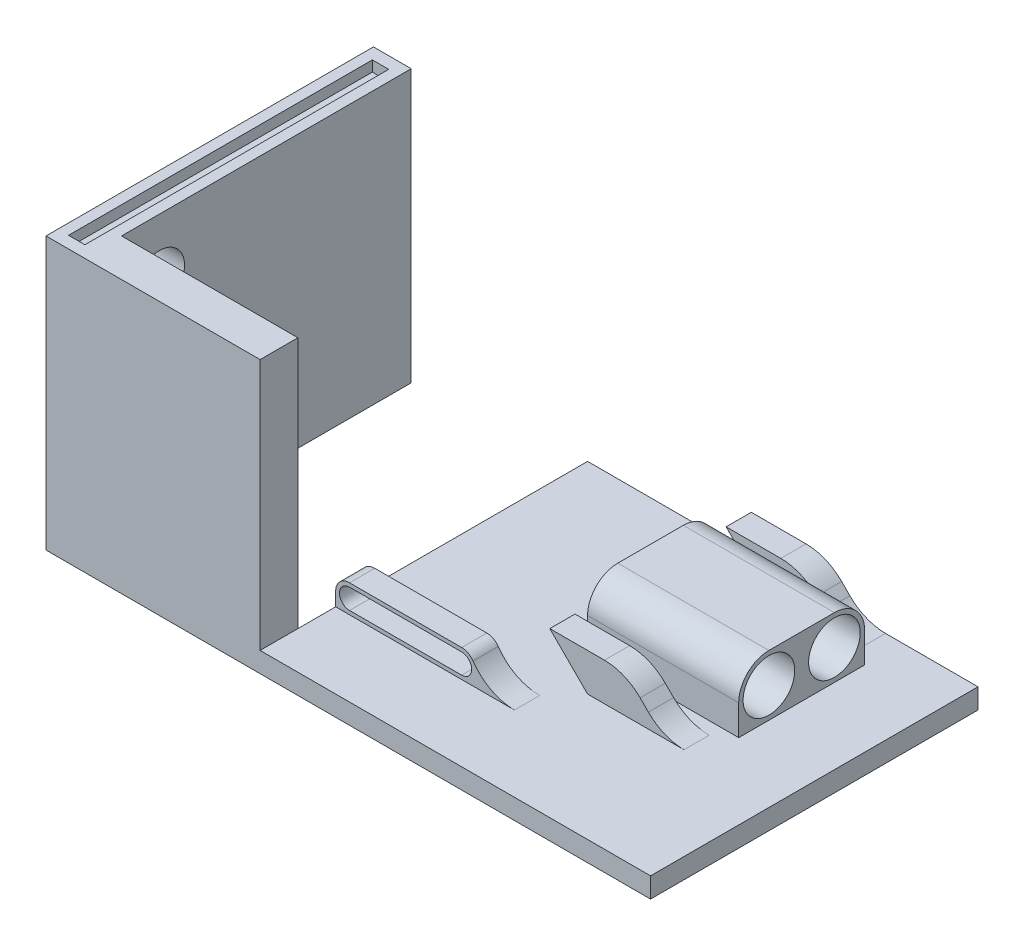
SolidWorks part; units mm, degrees
ref_plane "Front Plane" through (0, 0, 0) normal (0, 0, 1) x (1, 0, 0)
ref_plane "Top Plane" through (0, 0, 0) normal (0, 1, 0) x (1, 0, 0)
ref_plane "Right Plane" through (0, 0, 0) normal (1, 0, 0) x (0, 0, -1)
sketch "Sketch1" plane through (0, 0, 0) normal (0, 1, 0) x (1, 0, 0)
  line L1 (-82.5, -32.5) -> (82.5, -32.5)
  line L2 (-82.5, -32.5) -> (-82.5, 32.5)
  line L3 (-82.5, 32.5) -> (82.5, 32.5)
  line L4 (82.5, -32.5) -> (82.5, 32.5)
  line L5 (-82.5, -32.5) -> (82.5, 32.5) construction
  line L6 (-82.5, 32.5) -> (82.5, -32.5) construction
  point P0 (0, 0)
  dimension "D1" = 165
  dimension "D2" = 65
extrude "Boss-Extrude1" add sketch "Sketch1" along normal blind 4
sketch "Sketch2" plane through (0, 4, 0) normal (0, 1, 0) x (1, 0, 0)
  line L0 (-82.5, -32.5) -> (-125, -32.5)
  line L1 (-125, -32.5) -> (-125, 32.5)
  line L2 (-125, 32.5) -> (-117.5, 32.5)
  line L3 (-117.5, 32.5) -> (-117.5, -25)
  line L4 (-117.5, -25) -> (-82.5, -25)
  line L5 (-82.5, 32.5) -> (-82.5, -32.5) construction
  line L6 (82.5, 32.5) -> (-82.5, 32.5) construction
  line L7 (-82.5, -25) -> (-82.5, -32.5)
  dimension "D1" = 7.5
  dimension "D2" = 7.5
  dimension "D3" = 35
extrude "Boss-Extrude2" add sketch "Sketch2" against normal up to surface (4 mm away) and the other way blind 50 up to face at (0, 0, 0)
sketch "Sketch3" plane through (0, 0, 32.5) normal (0, 0, 1) x (1, 0, 0)
  line L0 (-79.75, 6.75) -> (-57.5, 6.75) construction
  line L1 (-79.75, 9.5) -> (-57.5, 9.5)
  line L2 (-82.5, 4) -> (-57.5, 4)
  line L3 (-79.75, 6.75) -> (-57.5, 6.75) construction
  line L4 (-79.75, 8.75) -> (-57.5, 8.75)
  line L5 (-79.75, 4.75) -> (-57.5, 4.75)
  line L6 (-82.5, 4) -> (82.5, 4) construction
  line L7 (-82.5, 54) -> (-82.5, 4) construction
  line L8 (0, 0) -> (0, 4) construction
  line L9 (-82.5, 4) -> (-82.5, 0) construction
  line L10 (-125, 0) -> (82.5, 0) construction
  line L13 (-82.5, 6.75) -> (-82.5, 4)
  arc A4 (-57.5, 4) -> (-57.5, 9.5) centre (-57.5, 6.75) ccw
  arc A5 (-79.75, 8.75) -> (-79.75, 4.75) centre (-79.75, 6.75) ccw
  arc A6 (-57.5, 4.75) -> (-57.5, 8.75) centre (-57.5, 6.75) ccw
  arc A7 (-82.5, 6.75) -> (-79.75, 9.5) centre (-79.75, 6.75) cw
  point P2 (-68.625, 6.75)
  point P9 (-68.625, 6.75)
  dimension "D1" = 2.75
  dimension "D2" = 2
  dimension "D3" = 2.75
  dimension "D5" = 2.75
  dimension "D4" = 25
extrude "Boss-Extrude4" add sketch "Sketch3" against normal blind 5 from offset 15 offset against normal yes
fillet "Fillet1" radius 10 1 edges at (-57.5, 4, 15)
fillet "Fillet2" [suppressed] radius 10
sketch "Sketch4" plane through (0, 0, -32.5) normal (0, 0, -1) x (-1, 0, 0)
  line L0 (27.5, 4) -> (35, 11.5)
  line L1 (-82.5, 4) -> (82.5, 4) construction
  line L2 (35, 11.5) -> (50, 11.5)
  line L4 (50, 11.5) -> (42.5, 4)
  line L5 (27.5, 4) -> (42.5, 4)
  dimension "D1" = 40
  dimension "D2" = 15
  dimension "D3" = 45
  dimension "D4" = 7.5
extrude "Boss-Extrude5" add sketch "Sketch4" against normal blind 5
fillet "Fillet3" radius 10 2 edges at (-35, 11.5, -30) (-27.5, 4, -30)
pattern_linear "LPattern1" count 2 spacing 35 along (0, 0, 1) of "Fillet3", "Boss-Extrude5"
sketch "Sketch5" plane through (0, 4, 0) normal (0, 1, 0) x (1, 0, 0)
  line L0 (82.5, 32.5) -> (82.5, -32.5)
  line L1 (82.5, -32.5) -> (0, -32.5)
  line L2 (-82.5, -32.5) -> (82.5, -32.5) construction
  line L3 (0, -32.5) -> (0, 32.5)
  line L4 (82.5, 32.5) -> (-23.3579, 32.5) construction
  line L5 (0, 32.5) -> (82.5, 32.5)
extrude "Cut-Extrude1" cut sketch "Sketch5" against normal blind 5
sketch "Sketch6" plane through (0, 0, 0) normal (1, 0, 0) x (0, 0, -1)
  line L0 (0, 10) -> (0, 4)
  line L1 (32.5, 4) -> (-32.5, 4) construction
  line L2 (0, 4) -> (25, 4)
  line L4 (-2.5, 8.5711) -> (-2.5, 6.9289) construction
  line L5 (6, 16) -> (19, 16)
  line L6 (25, 10) -> (25, 4)
  line L7 (27.5, 6.9289) -> (27.5, 4) construction
  circle A0 centre (6, 10) radius 5.125
  arc A2 (0, 10) -> (6, 16) centre (6, 10) cw
  arc A3 (19, 16) -> (25, 10) centre (19, 10) cw
  circle A4 centre (19, 10) radius 5.125
  dimension "D1" = 10.25
  dimension "D2" = 6
  dimension "D3" = 6
  dimension "D4" = 2.5
  dimension "D5" = 2.5
extrude "Boss-Extrude6" add sketch "Sketch6" against normal blind 30 from offset 20 offset against normal yes
sketch "Sketch13" plane through (0, 54, 0) normal (0, 1, 0) x (1, 0, 0)
  line L0 (-121.25, 32.5) -> (-121.25, -32.5) construction
  line L1 (-119.625, 30.15) -> (-122.875, 30.15)
  line L2 (-119.625, 30.15) -> (-119.625, -30.15)
  line L3 (-119.625, -30.15) -> (-122.875, -30.15)
  line L4 (-122.875, 30.15) -> (-122.875, -30.15)
  line L5 (-117.5, 32.5) -> (-125, 32.5) construction
  line L6 (-125, -32.5) -> (-82.5, -32.5) construction
  point P10 (-121.25, 30.15)
  dimension "D1" = 2.35
  dimension "D2" = 2.35
  dimension "D3" = 3.25
extrude "Cut-Extrude6" cut sketch "Sketch13" against normal blind 2.1
mirror "Mirror1" [suppressed] about plane through (0, 0, 0) normal (1, 0, 0)
sketch "Sketch7" plane through (0, 54, 0) normal (0, 1, 0) x (1, 0, 0)
  line L0 (-82.5, -32.5) -> (0, -32.5) construction
  line L1 (-125, 32.5) -> (0, 32.5)
  line L2 (-125, 32.5) -> (-125, -32.5)
  line L3 (-125, -32.5) -> (0, -32.5)
  line L4 (0, 32.5) -> (0, -32.5)
extrude "Cut-Extrude2" [suppressed] cut sketch "Sketch7" against normal up to surface (54 mm away)
sketch "Sketch8" plane through (-125, 0, 0) normal (-1, 0, 0) x (0, 0, 1)
  line L1 (32.5, 54) -> (32.5, 4) construction
  circle A0 centre (17.5, 42.7402) radius 5
  dimension "D2" = 10
  dimension "D1" = 15
extrude "Cut-Extrude3" cut sketch "Sketch8" against normal up to surface (7.5 mm away) up to face at (-117.5, 27, -3.75)
sketch "Sketch9" [suppressed] plane through (0, 0, 32.5) normal (0, 0, 1) x (1, 0, 0)
  line L1 (82.5, 4) -> (105, 4)
  line L2 (82.5, 4) -> (82.5, 54)
  line L3 (82.5, 54) -> (105, 54)
  line L4 (105, 4) -> (105, 54)
extrude "Cut-Extrude4" [suppressed] cut sketch "Sketch9" against normal through all
sketch "Sketch17" [suppressed] plane through (0, 0, 0) normal (0, -1, 0) x (1, 0, 0)
  line L0 (0, 32.5) -> (0, -32.5) construction
  line L1 (4, 32.5) -> (7.15, 32.5)
  line L2 (4, 32.5) -> (4, 29.35)
  line L3 (4, 29.35) -> (7.15, 29.35)
  line L4 (7.15, 32.5) -> (7.15, 29.35)
  line L5 (29, 32.5) -> (32.15, 32.5)
  line L6 (29, 32.5) -> (29, 29.35)
  line L7 (29, 29.35) -> (32.15, 29.35)
  line L8 (32.15, 32.5) -> (32.15, 29.35)
  line L10 (0, 32.5) -> (105, 32.5) construction
  dimension "D1" = 3.15
  dimension "D2" = 25
  dimension "D3" = 4
extrude "Cut-Extrude9" [suppressed] cut sketch "Sketch17" against normal blind 1
mirror "Mirror4" [suppressed] about plane through (0, 0, 0) normal (1, 0, 0)
sketch "Sketch10" [suppressed] plane through (0, 0, 32.5) normal (0, 0, 1) x (1, 0, 0)
  line L1 (0, 0) -> (105, 0)
  line L2 (0, 0) -> (0, 25)
  line L3 (0, 25) -> (105, 25)
  line L4 (105, 0) -> (105, 25)
  dimension "D1" = 25
extrude "Cut-Extrude5" [suppressed] cut sketch "Sketch10" against normal through all
sketch "Sketch11" [suppressed] plane through (0, 4, 0) normal (0, 1, 0) x (1, 0, 0)
  line L1 (-99.75, 30.25) -> (-102.75, 30.25)
  line L2 (-99.75, 30.25) -> (-99.75, -30.25)
  line L3 (-99.75, -30.25) -> (-102.75, -30.25)
  line L4 (-102.75, 30.25) -> (-102.75, -30.25)
  line L5 (-101.25, 32.5) -> (-101.25, -32.5) construction
  line L6 (-97.5, 32.5) -> (-105, 32.5) construction
  line L7 (0, -32.5) -> (105, -32.5) construction
  point P10 (-101.25, 30.25)
  dimension "D1" = 3
  dimension "D2" = 2.25
  dimension "D3" = 2.25
extrude "Boss-Extrude7" [suppressed] add sketch "Sketch11" along normal blind 2
sketch "Sketch12" [suppressed] plane through (0, 4, 0) normal (0, 1, 0) x (1, 0, 0)
  line L0 (101.25, 32.5) -> (101.25, -32.5) construction
  line L1 (99.75, -30.25) -> (102.75, -30.25)
  line L2 (99.75, -30.25) -> (99.75, 30.25)
  line L3 (99.75, 30.25) -> (102.75, 30.25)
  line L4 (102.75, -30.25) -> (102.75, 30.25)
  line L5 (97.5, 32.5) -> (105, 32.5) construction
  line L6 (0, -32.5) -> (105, -32.5) construction
  point P10 (101.25, -30.25)
  dimension "D1" = 2.25
  dimension "D2" = 2.25
  dimension "D3" = 3
extrude "Boss-Extrude8" [suppressed] add sketch "Sketch12" along normal blind 2
sketch "Sketch18" [suppressed] plane through (0, 0, 0) normal (0, -1, 0) x (1, 0, 0)
  line L0 (-105, 32.5) -> (0, 32.5) construction
  line L1 (-4, 32.5) -> (-7.15, 32.5)
  line L2 (-4, 32.5) -> (-4, 29.35)
  line L3 (-4, 29.35) -> (-7.15, 29.35)
  line L4 (-7.15, 32.5) -> (-7.15, 29.35)
  line L5 (0, -32.5) -> (0, 32.5) construction
  line L6 (-29, 32.5) -> (-32.15, 32.5)
  line L7 (-29, 32.5) -> (-29, 29.35)
  line L8 (-29, 29.35) -> (-32.15, 29.35)
  line L9 (-32.15, 32.5) -> (-32.15, 29.35)
  dimension "D1" = 3.15
  dimension "D2" = 4
  dimension "D3" = 25
extrude "Cut-Extrude10" [suppressed] cut sketch "Sketch18" against normal blind 1
sketch "Sketch19" plane through (0, 4, 0) normal (0, 1, 0) x (1, 0, 0)
  line L0 (0, 32.5) -> (0, -32.5) construction
  line L1 (0, -32.5) -> (-5, -32.5)
  line L2 (0, -32.5) -> (0, 32.5)
  line L3 (0, 32.5) -> (-5, 32.5)
  line L4 (-5, -32.5) -> (-5, 32.5)
  line L5 (0, 32.5) -> (-23.3579, 32.5) construction
  dimension "D1" = 5
extrude "Cut-Extrude11" cut sketch "Sketch19" against normal blind 10
